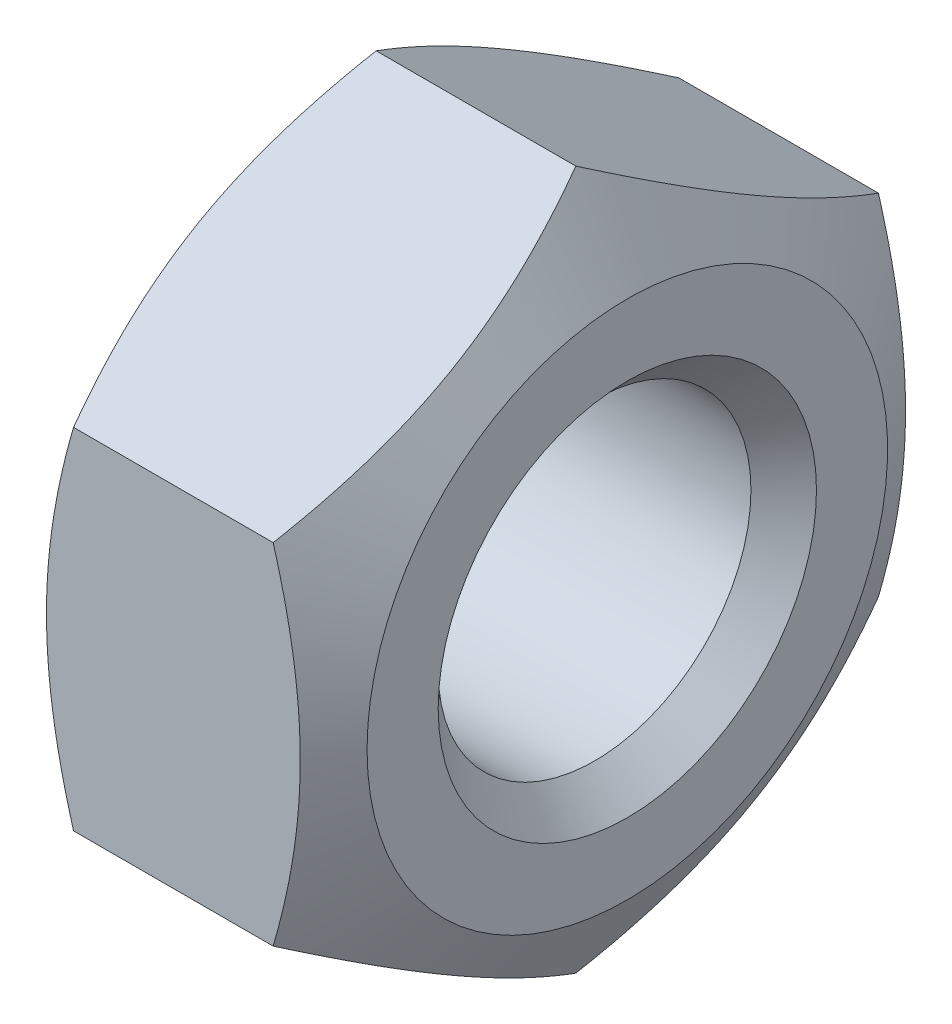
SolidWorks part; units mm, degrees
ref_plane "Front Plane" through (0, 0, 0) normal (0, 0, 1) x (1, 0, 0)
ref_plane "Top Plane" through (0, 0, 0) normal (0, 1, 0) x (1, 0, 0)
ref_plane "Right Plane" through (0, 0, 0) normal (1, 0, 0) x (0, 0, -1)
ref_plane "Plane1" through (0, 0, 0) normal (1, 0, 0) x (0, 0, -1)
sketch "Sketch1" plane through (0, 0, 0) normal (1, 0, 0) x (0, 0, -1)
  line L0 (-4, -2.3094) -> (0, -4.6188)
  line L1 (0, -4.6188) -> (4, -2.3094)
  line L2 (4, -2.3094) -> (4, 2.3094)
  line L3 (4, 2.3094) -> (0, 4.6188)
  line L4 (0, 4.6188) -> (-4, 2.3094)
  line L5 (-4, 2.3094) -> (-4, -2.3094)
extrude "Boss-Extrude1" add sketch "Sketch1" against normal blind 2 and the other way blind 2
ref_plane "Plane2" through (0, 0, 0) normal (0, 0, 1) x (1, 0, 0)
sketch "Sketch2" plane through (0, 0, 0) normal (0, 0, 1) x (1, 0, 0)
  line L0 (-2, 0) -> (-2, 2.5)
  line L1 (-2, 2.5) -> (-1.567, 2.067)
  line L2 (-1.567, 2.067) -> (1.567, 2.067)
  line L3 (1.567, 2.067) -> (2, 2.5)
  line L4 (2, 2.5) -> (2, 0)
  line L5 (2, 0) -> (-2, 0)
  line L6 (2, 0) -> (-2, 0) construction
revolve "Cut-Revolve1" cut sketch "Sketch2" angle 360 about L6 reverse direction yes
ref_plane "Plane3" through (0, 0, 0) normal (0, 0, 1) x (1, 0, 0)
sketch "Sketch3" plane through (0, 0, 0) normal (0, 0, 1) x (1, 0, 0)
  line L0 (-7, 1) -> (-2, 1)
  line L1 (-2, 1) -> (-2, 3.44)
  line L2 (-2, 3.44) -> (0, 6.9041)
  line L3 (0, 6.9041) -> (2, 3.44)
  line L4 (2, 3.44) -> (2, 1)
  line L5 (2, 1) -> (7, 1)
  line L6 (7, 1) -> (7, 8.44)
  line L7 (7, 8.44) -> (-7, 8.44)
  line L8 (-7, 8.44) -> (-7, 1)
  line L9 (50, 0) -> (-50, 0) construction
revolve "Cut-Revolve2" cut sketch "Sketch3" angle 360 about L9 reverse direction yes
